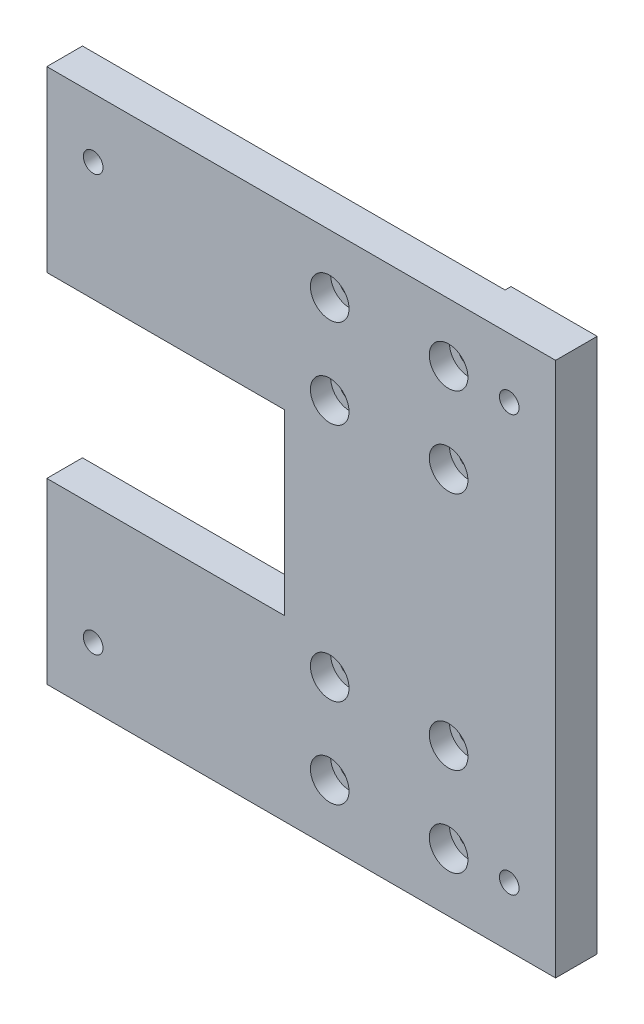
SolidWorks part; units mm, degrees
ref_plane "前视基准面" through (0, 0, 0) normal (0, 0, 1) x (1, 0, 0)
ref_plane "上视基准面" through (0, 0, 0) normal (0, 1, 0) x (1, 0, 0)
ref_plane "右视基准面" through (0, 0, 0) normal (1, 0, 0) x (0, 0, -1)
sketch "草图1" plane through (0, 0, 0) normal (0, 0, 1) x (1, 0, 0)
  line L1 (0, 0) -> (85.6, 0)
  line L2 (0, 0) -> (0, 90)
  line L3 (0, 90) -> (85.6, 90)
  line L4 (85.6, 0) -> (85.6, 90)
  dimension "D1" = 90
  dimension "D2" = 85.6
extrude "凸台-拉伸1" add sketch "草图1" along normal blind 6
sketch "草图2" plane through (0, 0, 6) normal (0, 0, 1) x (1, 0, 0)
  line L0 (85.6, 45) -> (0, 45) construction
  line L1 (85.6, 0) -> (85.6, 90) construction
  line L2 (0, 90) -> (0, 0) construction
  line L4 (0, 60) -> (40, 60)
  line L5 (0, 60) -> (0, 30)
  line L6 (0, 30) -> (40, 30)
  line L7 (40, 60) -> (40, 30)
  dimension "D1" = 40
  dimension "D2" = 30
extrude "切除-拉伸1" cut sketch "草图2" against normal through all
sketch "草图3" plane through (0, 0, 0) normal (0, 0, -1) x (-1, 0, 0)
  line L0 (0, 0) -> (-85.6, 0) construction
  line L1 (-85.6, 90) -> (-71.1, 90)
  line L2 (-85.6, 90) -> (-85.6, 0)
  line L3 (-85.6, 0) -> (-71.1, 0)
  line L4 (-71.1, 90) -> (-71.1, 0)
  dimension "D1" = 14.5
extrude "凸台-拉伸2" add sketch "草图3" along normal blind 1
hole_wizard "M3 六角凹头螺钉的柱形沉头孔1" positions "草图4" profile "草图5" counterbore size "M3" standard "ISO" end condition through all
sketch "草图4" plane through (0, 0, 6) normal (0, 0, 1) x (1, 0, 0)
  point P0 (67.6, 65.15)
  point P3 (47.6, 65.15)
  point P6 (67.6, 80.15)
  point P9 (47.6, 80.15)
sketch "草图5" plane through (67.6, 65.15, 6) normal (1, 0, 0) x (0, -1, 0)
  line L0 (0, 0) -> (0, 7)
  line L1 (0, 7) -> (1.7, 7)
  line L3 (1.7, 7) -> (1.7, 3.4)
  line L4 (1.7, 3.4) -> (3.25, 3.4)
  line L5 (3.25, 3.4) -> (3.25, 0)
  line L7 (3.25, 0) -> (0, 0)
  line L11 (0, -6.35) -> (0, 107.95) construction
  dimension "通孔孔直径" = 3.4
  dimension "通孔孔深度" = 7
  dimension "柱形沉头孔直径" = 6.5
  dimension "柱形沉头孔深度" = 3.4
ref_plane "基准面1" through (0, 45, 0) normal (0, 1, 0) x (1, 0, 0)
mirror "镜向1" about plane through (0, 45, 0) normal (0, 1, 0) of "M3 六角凹头螺钉的柱形沉头孔1"
hole_wizard "M4 螺纹孔1" positions "草图6" profile "草图7" tap size "M4" standard "ISO" end condition through all
sketch "草图6" plane through (0, 0, 6) normal (0, 0, 1) x (1, 0, 0)
  point P0 (77.8, 10)
  point P3 (7.8, 10)
  point P6 (77.8, 80)
  point P9 (7.8, 80)
sketch "草图7" plane through (77.8, 10, 6) normal (1, 0, 0) x (0, -1, 0)
  line L0 (0, 0) -> (0, 7)
  line L1 (0, 7) -> (1.65, 7)
  line L2 (1.65, 7) -> (1.65, 0)
  line L5 (1.65, 0) -> (0, 0)
  line L11 (0, -6.35) -> (0, 107.95) construction
  dimension "通孔螺纹孔钻头直径" = 3.3
  dimension "通孔螺纹孔钻头深度" = 7
cosmetic thread "孔螺蚊线1" parameters "D2"=4
cosmetic thread "孔螺蚊线2" parameters "D2"=4
cosmetic thread "孔螺蚊线3" parameters "D2"=4
cosmetic thread "孔螺蚊线4" parameters "D2"=4
